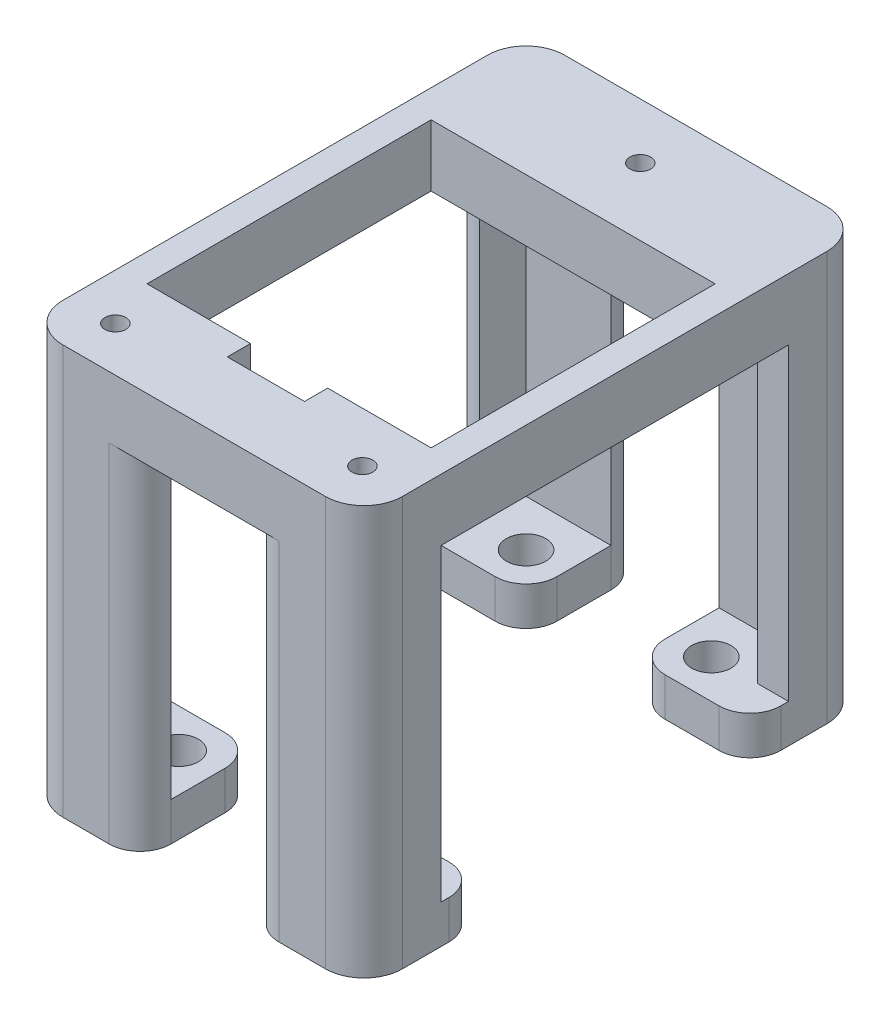
SolidWorks part; units mm, degrees
ref_plane "Front Plane" through (0, 0, 0) normal (0, 0, 1) x (1, 0, 0)
ref_plane "Top Plane" through (0, 0, 0) normal (0, 1, 0) x (1, 0, 0)
ref_plane "Right Plane" through (0, 0, 0) normal (1, 0, 0) x (0, 0, -1)
sketch "Sketch1" plane through (0, 0, 0) normal (0, 1, 0) x (1, 0, 0)
  line L0 (-22, 32.5) -> (22, -32.5) construction
  line L1 (-22, 32.5) -> (22, 32.5)
  line L2 (-22, 32.5) -> (-22, -32.5)
  line L3 (-22, -32.5) -> (22, -32.5)
  line L4 (22, 32.5) -> (22, -32.5)
  dimension "D1" = 44
  dimension "D2" = 65
extrude "Boss-Extrude1" add sketch "Sketch1" along normal blind 8
sketch "Sketch2" plane through (0, 8, 0) normal (0, 1, 0) x (1, 0, 0)
  line L0 (-22, -32.5) -> (22, -32.5) construction
  line L1 (-18.4, 16.6) -> (18.4, 16.6)
  line L2 (-18.4, 16.6) -> (-18.4, -20.2)
  line L3 (-18.4, -20.2) -> (18.4, -20.2)
  line L4 (18.4, 16.6) -> (18.4, -20.2)
  dimension "D1" = 36.8
  dimension "D2" = 36.8
  dimension "D3" = 18.4
  dimension "D4" = 12.3
extrude "Cut-Extrude1" cut sketch "Sketch2" against normal up to next
sketch "Sketch3" plane through (0, 8, 0) normal (0, 1, 0) x (1, 0, 0)
  line L0 (18.4, 16.6) -> (-18.4, 16.6) construction
  line L1 (-22, 32.5) -> (-22, -32.5) construction
  circle A0 centre (-16, -26.7) radius 1.35
  circle A1 centre (16, -26.7) radius 1.35
  circle A2 centre (0, 25.3) radius 1.35
  dimension "D1" = 32
  dimension "D2" = 52
  dimension "D4" = 2.7
  dimension "D5" = 22
  dimension "D6" = 16
  dimension "D3" = 8.7
extrude "Cut-Extrude2" cut sketch "Sketch3" against normal up to next
sketch "Sketch5" plane through (0, 0, 0) normal (0, -1, 0) x (1, 0, 0)
  line L0 (22, 32.5) -> (7, 32.5)
  line L1 (-22, 32.5) -> (22, 32.5) construction
  line L2 (7, 32.5) -> (7, 28.5)
  line L3 (7, 28.5) -> (18, 28.5)
  line L4 (18, 28.5) -> (18, 22.5)
  line L5 (18, 22.5) -> (22, 22.5)
  line L6 (22, 32.5) -> (22, -32.5) construction
  line L7 (22, 22.5) -> (22, 32.5)
  dimension "D1" = 15
  dimension "D2" = 10
  dimension "D3" = 4
  dimension "D4" = 4
extrude "Boss-Extrude2" add sketch "Sketch5" along normal blind 40
sketch "Sketch6" plane through (0, -40, 0) normal (0, -1, 0) x (1, 0, 0)
  line L1 (22, 32.5) -> (7, 32.5)
  line L2 (22, 32.5) -> (22, 17.5)
  line L3 (22, 17.5) -> (7, 17.5)
  line L4 (7, 32.5) -> (7, 17.5)
  dimension "D1" = 15
  dimension "D2" = 15
extrude "Boss-Extrude3" add sketch "Sketch6" along normal blind 5
sketch "Sketch7" plane through (0, -40, 0) normal (0, 1, 0) x (1, 0, 0)
  circle A0 centre (12, -22.5) radius 2.55
  dimension "D1" = 5.1
  dimension "D2" = 22.5
  dimension "D3" = 12
extrude "Cut-Extrude3" cut sketch "Sketch7" against normal up to next
mirror "Mirror1" about plane through (0, 0, 0) normal (1, 0, 0) of "Cut-Extrude3", "Boss-Extrude3", "Boss-Extrude2"
mirror "Mirror2" about plane through (0, 0, 0) normal (0, 0, 1) of "Mirror1", "Boss-Extrude2", "Boss-Extrude3", "Cut-Extrude3"
sketch "Sketch8" plane through (0, 8, 0) normal (0, 1, 0) x (1, 0, 0)
  line L0 (-18.4, -20.2) -> (18.4, -20.2) construction
  line L1 (-5, -20.2) -> (5, -20.2)
  line L2 (-5, -20.2) -> (-5, -23.2)
  line L3 (-5, -23.2) -> (5, -23.2)
  line L4 (5, -20.2) -> (5, -23.2)
  dimension "D1" = 10
  dimension "D2" = 3
  dimension "D3" = 5
extrude "Cut-Extrude4" cut sketch "Sketch8" against normal up to next
fillet "Fillet1" radius 4 13 edges at (7, -22.5, 32.5) (22, -42.5, 17.5) (7, -42.5, 17.5) (7, -22.5, -32.5) (7, -42.5, -17.5) (22, -42.5, -17.5) (-7, -42.5, -17.5) (-22, -42.5, -17.5) (-7, -22.5, -32.5) (-22, -20, -22.5) (-7, -42.5, 17.5) (-22, -42.5, 17.5) (-7, -22.5, 32.5)
fillet "Fillet2" radius 5 4 edges at (22, -18.5, -32.5) (22, -18.5, 32.5) (-22, -18.5, 32.5) (-22, -18.5, -32.5)
